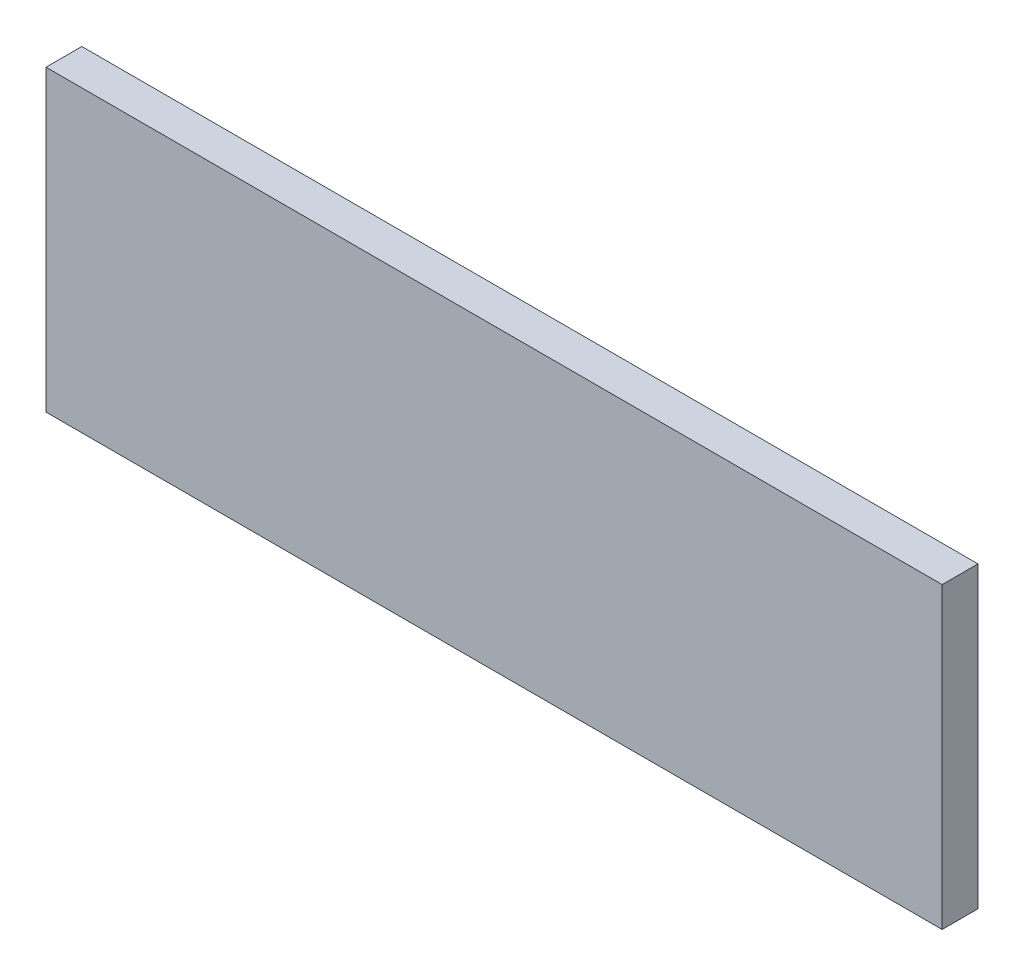
SolidWorks part; units mm, degrees
ref_plane "Ön Düzlem" through (0, 0, 0) normal (0, 0, 1) x (1, 0, 0)
ref_plane "Üst Düzlem" through (0, 0, 0) normal (0, 1, 0) x (1, 0, 0)
ref_plane "Sağ Düzlem" through (0, 0, 0) normal (1, 0, 0) x (0, 0, -1)
sketch "Çizim1" plane through (0, 0, 0) normal (0, 0, 1) x (1, 0, 0)
  line L1 (0, 0) -> (300, 0)
  line L2 (0, 0) -> (0, -100)
  line L3 (0, -100) -> (300, -100)
  line L4 (300, 0) -> (300, -100)
  dimension "D1" = 300
  dimension "D2" = 100
base flange "Taban-Flanş1" sketch "Çizim1" thickness 12 reverse thickness direction no parameters "D1"=6
sketch "Büküm-Çizgileri1" [suppressed] plane through (0, 0, 0) normal (0, 1, 0) x (1, 0, 0)
sketch "Sınırlandırma-Kutusu1" [suppressed] plane through (0, 0, 0) normal (0, 1, 0) x (1, 0, 0)
sheet metal parameters "Sac-Levha1" thickness 12 parameters "D1"=6
flat pattern "Düz-Çoğaltma1" [suppressed]
sketch "Büküm-Çizgileri2" plane through (0, 0, 0) normal (0, 1, 0) x (1, 0, 0)
sketch3d "Sınırlandırma-Kutusu2" [suppressed]
  line L0 (0, -100, 0) -> (300, -100, 0) construction
  line L1 (0, 0, 0) -> (300, 0, 0) construction
  line L2 (0, -100, 0) -> (0, 0, 0) construction
  line L3 (300, -100, 0) -> (300, 0, 0) construction
